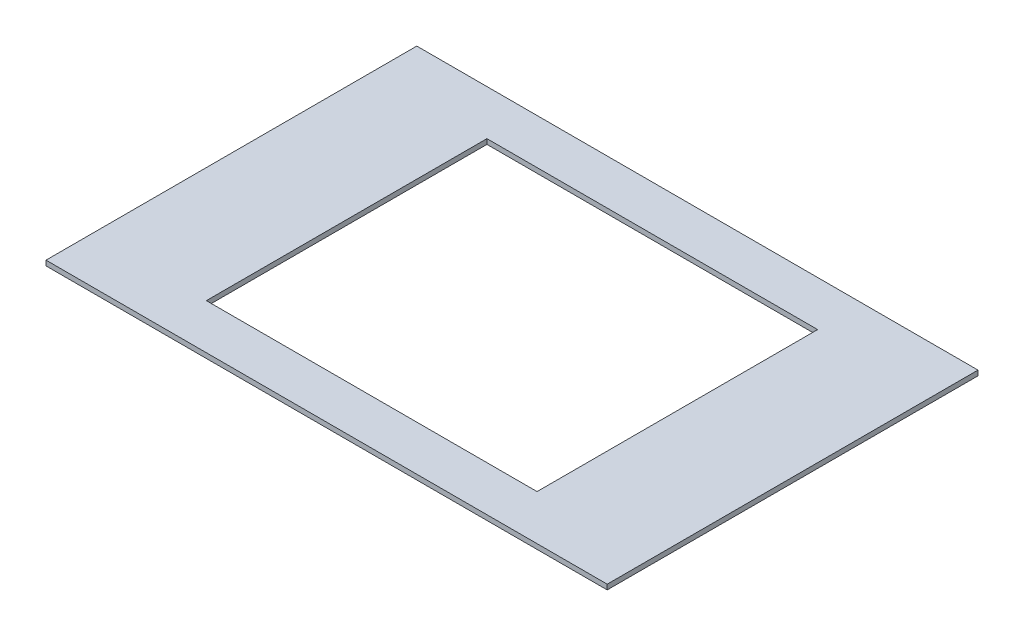
SolidWorks part; units mm, degrees
ref_plane "Front Plane" through (0, 0, 0) normal (0, 0, 1) x (1, 0, 0)
ref_plane "Top Plane" through (0, 0, 0) normal (0, 1, 0) x (1, 0, 0)
ref_plane "Right Plane" through (0, 0, 0) normal (1, 0, 0) x (0, 0, -1)
sketch "Sketch1" plane through (0, 0, 0) normal (0, 1, 0) x (1, 0, 0)
  line L1 (-56, 37) -> (56, 37)
  line L2 (-56, 37) -> (-56, -37)
  line L3 (-56, -37) -> (56, -37)
  line L4 (56, 37) -> (56, -37)
  line L5 (-56, 37) -> (56, -37) construction
  line L6 (-56, -37) -> (56, 37) construction
  point P0 (0, 0)
  dimension "D1" = 112
  dimension "D2" = 74
extrude "Boss-Extrude1" add sketch "Sketch1" along normal blind 1
sketch "Sketch5" plane through (0, 1, 0) normal (0, 1, 0) x (1, 0, 0)
  line L1 (-33, 28) -> (33, 28)
  line L2 (-33, 28) -> (-33, -28)
  line L3 (-33, -28) -> (33, -28)
  line L4 (33, 28) -> (33, -28)
  line L5 (-33, 28) -> (33, -28) construction
  line L6 (-33, -28) -> (33, 28) construction
  point P0 (0, 0)
  dimension "D1" = 66
  dimension "D2" = 56
extrude "Cut-Extrude2" cut sketch "Sketch5" against normal blind 1
